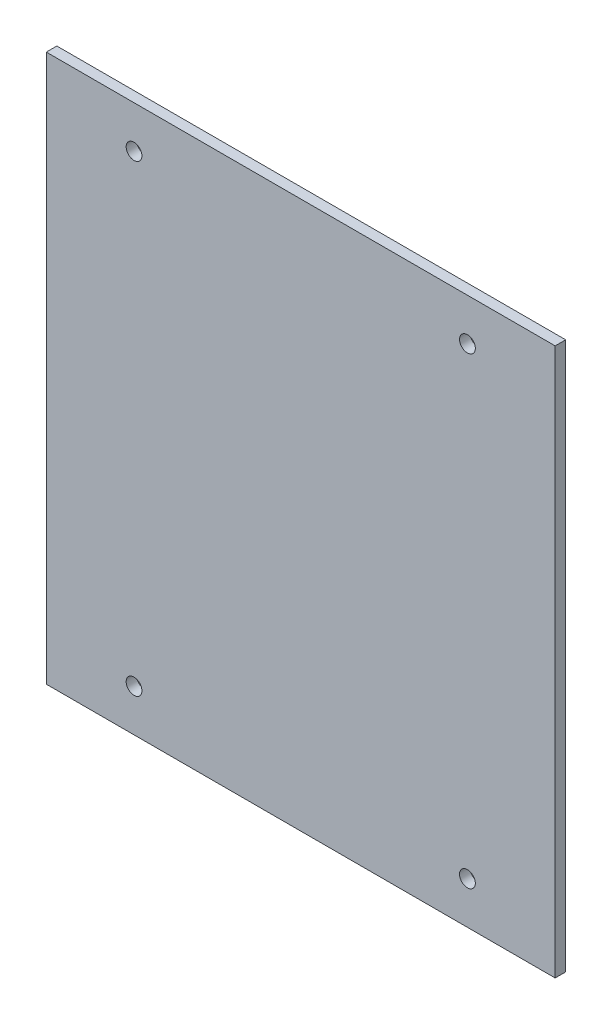
SolidWorks part; units mm, degrees
ref_plane "Ebene vorne" through (0, 0, 0) normal (0, 0, 1) x (1, 0, 0)
ref_plane "Ebene oben" through (0, 0, 0) normal (0, 1, 0) x (1, 0, 0)
ref_plane "Ebene rechts" through (0, 0, 0) normal (1, 0, 0) x (0, 0, -1)
sketch "Skizze1" plane through (0, 0, 0) normal (0, 0, 1) x (1, 0, 0)
  line L1 (72.5, -78) -> (-72.5, -78)
  line L2 (72.5, -78) -> (72.5, 78)
  line L3 (72.5, 78) -> (-72.5, 78)
  line L4 (-72.5, -78) -> (-72.5, 78)
  line L5 (72.5, -78) -> (-72.5, 78) construction
  line L6 (72.5, 78) -> (-72.5, -78) construction
  point P0 (0, 0)
  dimension "D1" = 156
  dimension "D2" = 145
extrude "Aufsatz-Linear austragen1" add sketch "Skizze1" along normal blind 3
hole_wizard "Durchgangsloch für M41" positions "Skizze2" profile "Skizze3" hole size "M4" standard "DIN"
sketch "Skizze2" plane through (0, 0, 3) normal (0, 0, 1) x (1, 0, 0)
  line L0 (-72.5, 78) -> (-72.5, -78) construction
  line L3 (-72.5, -78) -> (72.5, -78) construction
  line L4 (72.5, -78) -> (72.5, 78) construction
  line L5 (55, 0) -> (-55, 0) construction
  point P6 (-47.5, -66)
  point P25 (47.5, -66)
  point P35 (0, 0)
  point P38 (47.5, 66)
  point P39 (-47.5, 66)
  dimension "D3" = 25
  dimension "D4" = 12
  dimension "D5" = 25
  dimension "D6" = 12
sketch "Skizze3" plane through (-47.5, -66, 3) normal (1, 0, 0) x (0, -1, 0)
  line L0 (0, 0) -> (0, 4.3519)
  line L1 (0, 4.3519) -> (2.25, 3)
  line L2 (2.25, 3) -> (2.25, 0)
  line L5 (2.25, 0) -> (0, 0)
  line L10 (0, 4.3519) -> (-2.25, 3) construction
  line L11 (0, -6.35) -> (0, 107.95) construction
  dimension "Bohrerdurchmesser" = 4.5
  dimension "Bohrungstiefe" = 3
  dimension "Spitzenwinkel" = 118
